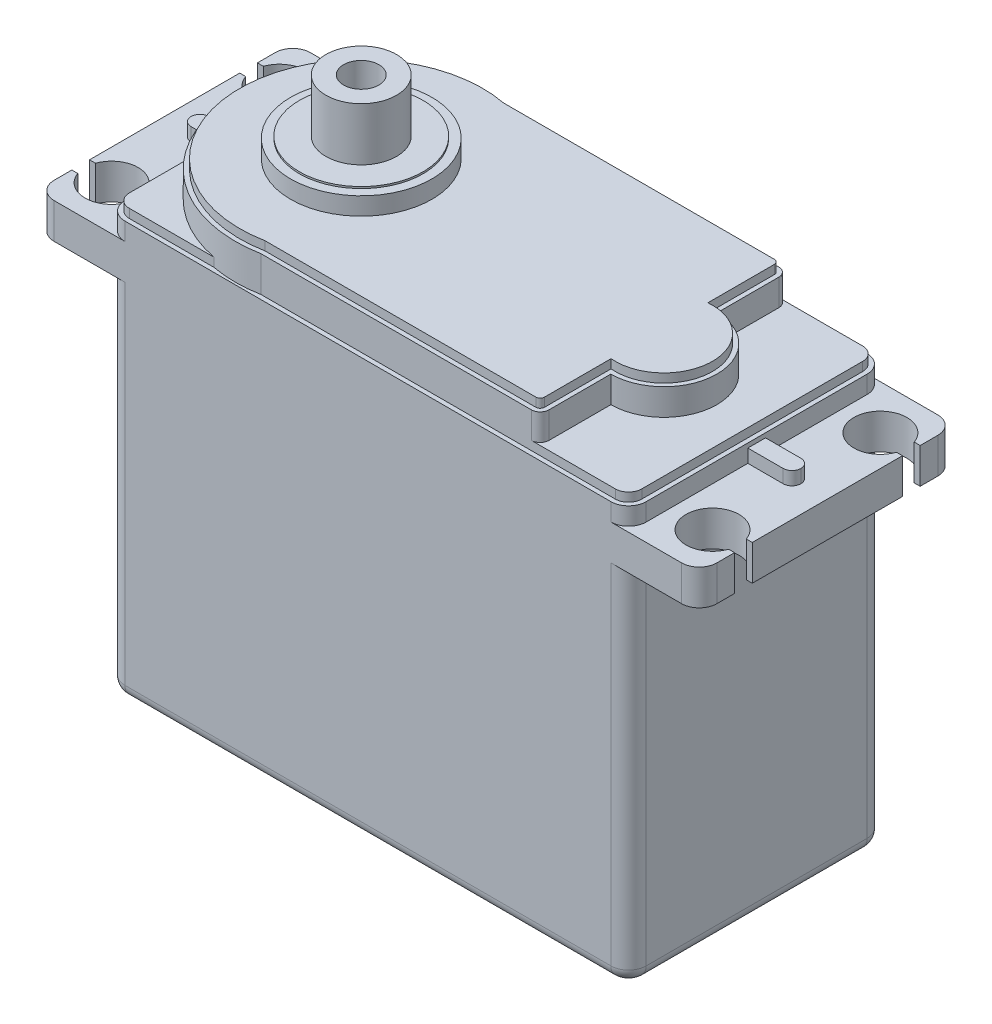
SolidWorks part; units mm, degrees
ref_plane "Front Plane" through (0, 0, 0) normal (0, 0, 1) x (1, 0, 0)
ref_plane "Top Plane" through (0, 0, 0) normal (0, 1, 0) x (1, 0, 0)
ref_plane "Right Plane" through (0, 0, 0) normal (1, 0, 0) x (0, 0, -1)
sketch "Sketch2" plane through (0, 0, 0) normal (0, 1, 0) x (1, 0, 0)
  line L1 (-29.5, -14.5) -> (29.5, -14.5)
  line L2 (-29.5, -14.5) -> (-29.5, 14.5)
  line L3 (-29.5, 14.5) -> (29.5, 14.5)
  line L4 (29.5, -14.5) -> (29.5, 14.5)
  line L5 (-29.5, -14.5) -> (29.5, 14.5) construction
  line L6 (-29.5, 14.5) -> (29.5, -14.5) construction
  point P0 (0, 0)
  dimension "D1" = 29
  dimension "D2" = 59
extrude "Boss-Extrude1" add sketch "Sketch2" along normal blind 47
fillet "Fillet1" radius 1.5 4 edges at (0, 0, -14.5) (29.5, 0, 0) (0, 0, 14.5) (-29.5, 0, 0)
sketch "Sketch3" plane through (29.5, 0, 0) normal (1, 0, 0) x (0, 0, -1)
  line L0 (-14.5, 47) -> (-14.5, 1.5) construction
  line L1 (-14.5, 45) -> (14.5, 45)
  line L2 (-14.5, 45) -> (-14.5, 41)
  line L3 (-14.5, 41) -> (14.5, 41)
  line L4 (14.5, 45) -> (14.5, 41)
  line L5 (14.5, 47) -> (14.5, 1.5) construction
  line L6 (-14.5, 47) -> (14.5, 47) construction
  dimension "D1" = 4
  dimension "D2" = 2
extrude "Boss-Extrude2" add sketch "Sketch3" along normal blind 8
sketch "Sketch4" plane through (0, 45, 0) normal (0, 1, 0) x (1, 0, 0)
  line L0 (29.5, 14.5) -> (29.5, -14.5) construction
  line L1 (37.5, -14.5) -> (29.5, -14.5) construction
  line L3 (36.8284, -8.5) -> (37.5, -8.5)
  line L4 (37.5, 14.5) -> (37.5, -14.5) construction
  line L5 (37.5, -8.5) -> (37.5, -10.5)
  line L6 (37.5, -10.5) -> (36.8284, -10.5)
  line L8 (37, -9.5) -> (37.5, -9.5) construction
  line L9 (37.5, 0) -> (29.5, 0) construction
  line L10 (37.5, 8.5) -> (37.5, 10.5)
  line L11 (37.5, 10.5) -> (36.8284, 10.5)
  line L14 (36.8284, 8.5) -> (37.5, 8.5)
  arc A0 (36.8284, -8.5) -> (36.8284, -10.5) centre (34, -9.5) ccw
  arc A1 (36.8284, 8.5) -> (36.8284, 10.5) centre (34, 9.5) cw
  dimension "D3" = 6
  dimension "D1" = 4.5
  dimension "D2" = 5
  dimension "D4" = 1
  dimension "D5" = 1
extrude "Cut-Extrude1" cut sketch "Sketch4" against normal blind 47
mirror "Mirror1" about plane through (0, 0, 0) normal (1, 0, 0) of "Cut-Extrude1", "Boss-Extrude2"
fillet "Fillet2" radius 2 4 edges at (-37.5, 43, 14.5) (-37.5, 43, -14.5) (37.5, 43, -14.5) (37.5, 43, 14.5)
sketch "Sketch6" plane through (0, 45, 0) normal (0, 1, 0) x (1, 0, 0)
  line L0 (29.5, 0) -> (37.5, 0) construction
  line L1 (29.5, -14.5) -> (29.5, 14.5) construction
  line L2 (37.5, 8.5) -> (37.5, -8.5) construction
  line L3 (29.5, -1) -> (29.5, 1)
  line L4 (29.5, 14.5) -> (29.5, -14.5) construction
  line L5 (29.5, 1) -> (34.5, 1)
  line L6 (34.5, 1) -> (34.5, -1)
  line L7 (34.5, -1) -> (29.5, -1)
  dimension "D1" = 1
  dimension "D2" = 2
  dimension "D3" = 5
extrude "Boss-Extrude3" add sketch "Sketch6" along normal blind 1.5
fillet "Fillet3" radius 1 2 edges at (34.5, 45.75, -1) (34.5, 45.75, 1)
mirror "Mirror2" about plane through (0, 0, 0) normal (1, 0, 0) of "Fillet3", "Boss-Extrude3"
fillet "Fillet4" radius 2 12 edges at (29.0607, 0.4393, 14.0607) (29.0607, 0.4393, -14.0607) (-29.0607, 0.4393, -14.0607) (-29.0607, 0.4393, 14.0607) (-29.5, 46, 14.5) (-29.5, 21.25, 14.5) (-29.5, 46, -14.5) (-29.5, 21.25, -14.5) (29.5, 46, -14.5) (29.5, 21.25, -14.5) (29.5, 46, 14.5) (29.5, 21.25, 14.5)
sketch "Sketch7" plane through (0, 47, 0) normal (0, 1, 0) x (1, 0, 0)
  line L8 (-29, 12.5) -> (-29, -12.5)
  line L9 (-27.5, -14) -> (27.5, -14)
  line L10 (29, -12.5) -> (29, 12.5)
  line L11 (27.5, 14) -> (-27.5, 14)
  line L12 (-29, 12.5) -> (-29, -12.5)
  line L13 (-27.5, -14) -> (27.5, -14)
  line L14 (29, -12.5) -> (29, 12.5)
  line L15 (27.5, 14) -> (-27.5, 14)
  arc A8 (-29, -12.5) -> (-27.5, -14) centre (-27.5, -12.5) ccw
  arc A9 (27.5, -14) -> (29, -12.5) centre (27.5, -12.5) ccw
  arc A10 (29, 12.5) -> (27.5, 14) centre (27.5, 12.5) ccw
  arc A11 (-27.5, 14) -> (-29, 12.5) centre (-27.5, 12.5) ccw
  arc A12 (-29, -12.5) -> (-27.5, -14) centre (-27.5, -12.5) ccw
  arc A13 (27.5, -14) -> (29, -12.5) centre (27.5, -12.5) ccw
  arc A14 (29, 12.5) -> (27.5, 14) centre (27.5, 12.5) ccw
  arc A15 (-27.5, 14) -> (-29, 12.5) centre (-27.5, 12.5) ccw
  dimension "D1" = 0.5
extrude "Boss-Extrude4" add sketch "Sketch7" along normal blind 1
sketch "Sketch8" plane through (0, 48, 0) normal (0, 1, 0) x (1, 0, 0)
  line L0 (-27.5, -14) -> (27.5, -14) construction
  line L1 (19, -14) -> (-12.5925, -14)
  line L2 (19, -14) -> (19, -6)
  line L3 (19, 14) -> (-12.5925, 14)
  line L6 (29, -12.5) -> (29, 12.5) construction
  line L8 (-29.5, 12.5) -> (-29.5, -12.5) construction
  line L9 (19, 6) -> (19, 14)
  arc A0 (-12.5925, 14) -> (-12.5925, -14) centre (-15.25, 0) ccw
  arc A1 (19, -6) -> (19, 6) centre (19, 0) ccw
  dimension "D3" = 28.5
  dimension "D4" = 12
  dimension "D1" = 10
extrude "Boss-Extrude6" add sketch "Sketch8" along normal blind 3
sketch "Sketch10" plane through (0, 48, 0) normal (0, -1, 0) x (1, 0, 0)
  line L1 (-17.9075, 14) -> (-12.5925, 14)
  line L2 (-17.9075, 14) -> (-12.5925, 14)
  arc A1 (-12.5925, 14) -> (-17.9075, 14) centre (-15.25, 0) ccw
  arc A2 (-12.5925, 14) -> (-17.9075, 14) centre (-15.25, 0) ccw
  dimension "D1" = 0
extrude "Boss-Extrude8" add sketch "Sketch10" along normal up to next
sketch "Sketch11" plane through (0, 48, 0) normal (0, -1, 0) x (1, 0, 0)
  line L1 (-29, -3.7417) -> (-29, 3.7417)
  line L2 (-29, -3.7417) -> (-29, 3.7417)
  arc A1 (-29, 3.7417) -> (-29, -3.7417) centre (-15.25, 0) ccw
  arc A2 (-29, 3.7417) -> (-29, -3.7417) centre (-15.25, 0) ccw
  dimension "D1" = 0
extrude "Boss-Extrude9" add sketch "Sketch11" along normal up to next
sketch "Sketch12" plane through (0, 48, 0) normal (0, -1, 0) x (1, 0, 0)
  line L1 (-12.5925, -14) -> (-17.9075, -14)
  line L2 (-12.5925, -14) -> (-17.9075, -14)
  arc A1 (-17.9075, -14) -> (-12.5925, -14) centre (-15.25, 0) ccw
  arc A2 (-17.9075, -14) -> (-12.5925, -14) centre (-15.25, 0) ccw
  dimension "D1" = 0
extrude "Boss-Extrude10" add sketch "Sketch12" along normal up to next
fillet "Fillet5" radius 1 2 edges at (19, 49.5, -14) (19, 49.5, 14)
sketch "Sketch13" plane through (0, 51, 0) normal (0, 1, 0) x (1, 0, 0)
  line L8 (18.5, 5.4772) -> (18.5, 13)
  line L9 (18, 13.5) -> (-12.6399, 13.5)
  line L10 (-12.6399, -13.5) -> (18, -13.5)
  line L11 (18.5, -13) -> (18.5, -5.4772)
  line L12 (18.5, 5.4772) -> (18.5, 13)
  line L13 (18, 13.5) -> (-12.6399, 13.5)
  line L14 (-12.6399, -13.5) -> (18, -13.5)
  line L15 (18.5, -13) -> (18.5, -5.4772)
  arc A8 (18.5, 13) -> (18, 13.5) centre (18, 13) ccw
  arc A9 (-12.6399, 13.5) -> (-12.6399, -13.5) centre (-15.25, 0) ccw
  arc A10 (18, -13.5) -> (18.5, -13) centre (18, -13) ccw
  arc A11 (18.5, -5.4772) -> (18.5, 5.4772) centre (19, 0) ccw
  arc A12 (18.5, 13) -> (18, 13.5) centre (18, 13) ccw
  arc A13 (-12.6399, 13.5) -> (-12.6399, -13.5) centre (-15.25, 0) ccw
  arc A14 (18, -13.5) -> (18.5, -13) centre (18, -13) ccw
  arc A15 (18.5, -5.4772) -> (18.5, 5.4772) centre (19, 0) ccw
  dimension "D1" = 0.5
extrude "Boss-Extrude11" add sketch "Sketch13" along normal blind 1
sketch "Sketch14" plane through (0, 52, 0) normal (0, 1, 0) x (1, 0, 0)
sketch "Sketch15" plane through (0, 52, 0) normal (0, 1, 0) x (1, 0, 0)
  circle A0 centre (-15.25, 0) radius 8
  arc A1 (-12.5925, 14) -> (-12.5925, -14) centre (-15.25, 0) ccw construction
  point P5 (-29.5, 0)
  dimension "D2" = 16
  dimension "D1" = 14.25
extrude "Boss-Extrude12" add sketch "Sketch15" along normal blind 2
sketch "Sketch16" plane through (0, 54, 0) normal (0, 1, 0) x (1, 0, 0)
  circle A0 centre (-15.25, 0) radius 7
  dimension "D1" = 14
extrude "Boss-Extrude13" add sketch "Sketch16" along normal blind 0.2
sketch "Sketch17" plane through (0, 54.2, 0) normal (0, 1, 0) x (1, 0, 0)
  circle A0 centre (-15.25, 0) radius 4
  dimension "D1" = 8
extrude "Boss-Extrude14" add sketch "Sketch17" along normal blind 6
sketch "Sketch18" plane through (0, 60.2, 0) normal (0, 1, 0) x (1, 0, 0)
  circle A0 centre (-15.25, 0) radius 2
  dimension "D1" = 4
extrude "Cut-Extrude2" cut sketch "Sketch18" against normal blind 4
